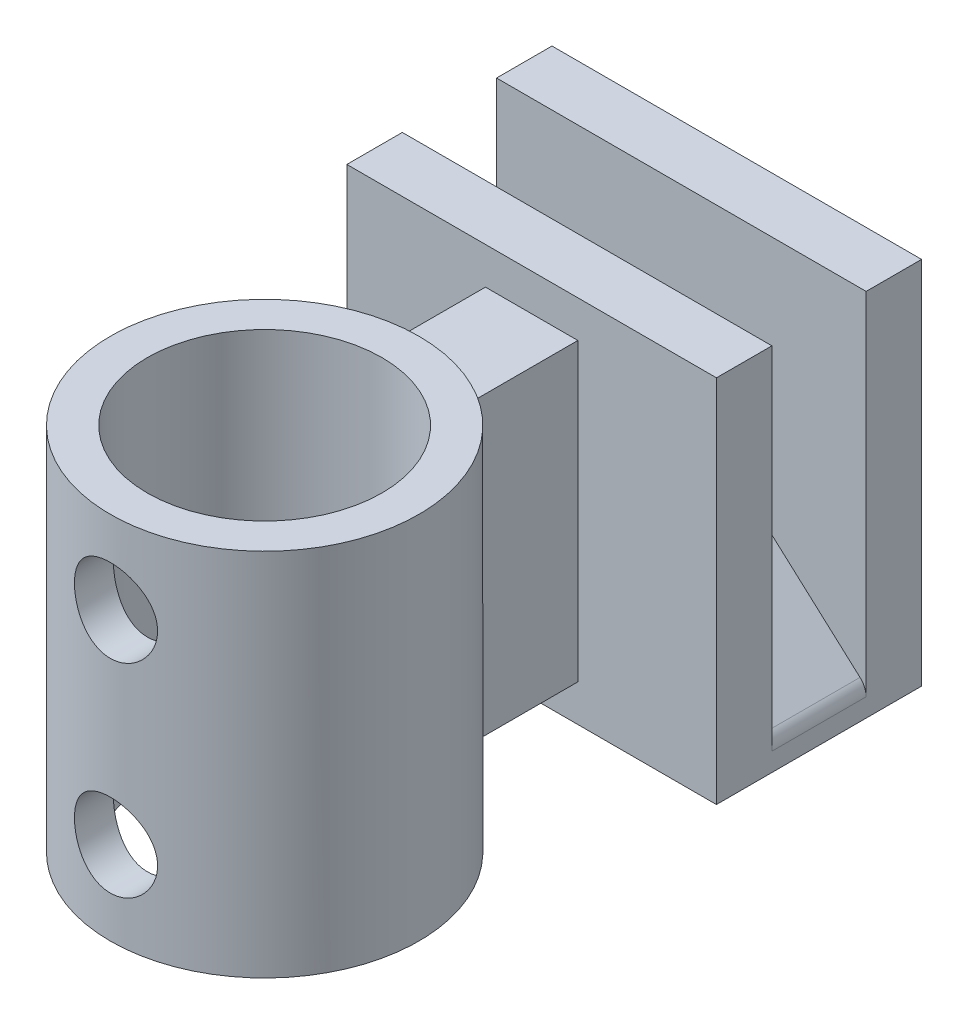
SolidWorks part; units mm, degrees
ref_plane "Front Plane" through (0, 0, 0) normal (0, 0, 1) x (1, 0, 0)
ref_plane "Top Plane" through (0, 0, 0) normal (0, 1, 0) x (1, 0, 0)
ref_plane "Right Plane" through (0, 0, 0) normal (1, 0, 0) x (0, 0, -1)
sketch "Sketch2" plane through (0, 0, 0) normal (0, 0, 1) x (1, 0, 0)
  line L1 (-10, -5) -> (10, -5)
  line L2 (-10, -5) -> (-10, 5)
  line L3 (-10, 5) -> (10, 5)
  line L4 (10, -5) -> (10, 5)
  line L5 (-10, -5) -> (10, 5) construction
  line L6 (-10, 5) -> (10, -5) construction
  point P0 (0, 0)
  dimension "D1" = 10
  dimension "D2" = 20
extrude "Boss-Extrude1" add sketch "Sketch2" along normal mid plane 5.1
chamfer "Chamfer1" distance 9.5 angle 42 2 edges at (10, 5, 0) (-10, 5, 0) first distance on face at (0, 5, 0)
fillet "Fillet3" radius 1 4 edges at (-10, -3.5538, 0) (10, -3.5538, 0) (0.5, 5, 0) (-0.5, 5, 0)
sketch "Sketch3" plane through (0, 0, 2.55) normal (0, 0, 1) x (1, 0, 0)
  line L0 (-10, -5) -> (10, -5) construction
  line L1 (-10, 15) -> (10, 15)
  line L2 (-10, 15) -> (-10, -5)
  line L3 (-10, -5) -> (10, -5)
  line L4 (10, 15) -> (10, -5)
  line L5 (-10, 15) -> (10, -5) construction
  line L6 (-10, -5) -> (10, 15) construction
  point P0 (0, 5)
  point P5 (0, 0)
  dimension "D1" = 20
  dimension "D2" = 20
extrude "Boss-Extrude2" add sketch "Sketch3" along normal blind 3
mirror "Mirror1" about plane through (0, 0, 0) normal (0, 0, 1) of "Boss-Extrude2"
sketch "Sketch6" plane through (0, 0, 0) normal (0, 1, 0) x (1, 0, 0)
  circle A0 centre (0, -20) radius 6.35
  circle A1 centre (0, -20) radius 8.35
  point P3 (1.8084, -19.9181)
  point P5 (0, 0)
  point P6 (0, 0)
  dimension "D1" = 12.7
  dimension "D2" = 2
  dimension "D3" = 20
extrude "Boss-Extrude3" add sketch "Sketch6" along normal up to surface and the other way up to surface separate body up to face at (0, 15, 4.05) other way up to face at (0, -5, 0)
sketch "Sketch5" plane through (0, 0, 5.55) normal (0, 0, 1) x (1, 0, 0)
  line L0 (-10, -5) -> (10, -5) construction
  line L1 (-2.5, 13) -> (2.5, 13)
  line L2 (-2.5, 13) -> (-2.5, -3)
  line L3 (-2.5, -3) -> (2.5, -3)
  line L4 (2.5, 13) -> (2.5, -3)
  line L5 (-2.5, 13) -> (2.5, -3) construction
  line L6 (-2.5, -3) -> (2.5, 13) construction
  line L7 (10, 15) -> (-10, 15) construction
  point P0 (0, 5)
  point P5 (0, 0)
  dimension "D1" = 2
  dimension "D2" = 2
  dimension "D3" = 5
extrude "Boss-Extrude4" add sketch "Sketch5" along normal up to surface (6.483 mm away) up to face at (0, 15, 11.65)
ref_plane "Plane1" through (0, 0, 20) normal (0, 0, 1) x (1, 0, 0)
sketch "Sketch7" plane through (0, 0, 20) normal (0, 0, 1) x (1, 0, 0)
  line L0 (-8.35, -5) -> (8.35, -5) construction
  line L1 (6.35, 15) -> (-6.35, 15) construction
  circle A0 centre (0, 10.5) radius 2.25
  circle A1 centre (0, -0.5) radius 2.25
  point P4 (0, 0)
  dimension "D1" = 4.5
  dimension "D2" = 4.5
  dimension "D3" = 4.5
  dimension "D4" = 4.5
extrude "Cut-Extrude1" cut sketch "Sketch7" along normal up to surface (8.0412 mm away) up to face at (0, 15, 11.65)
